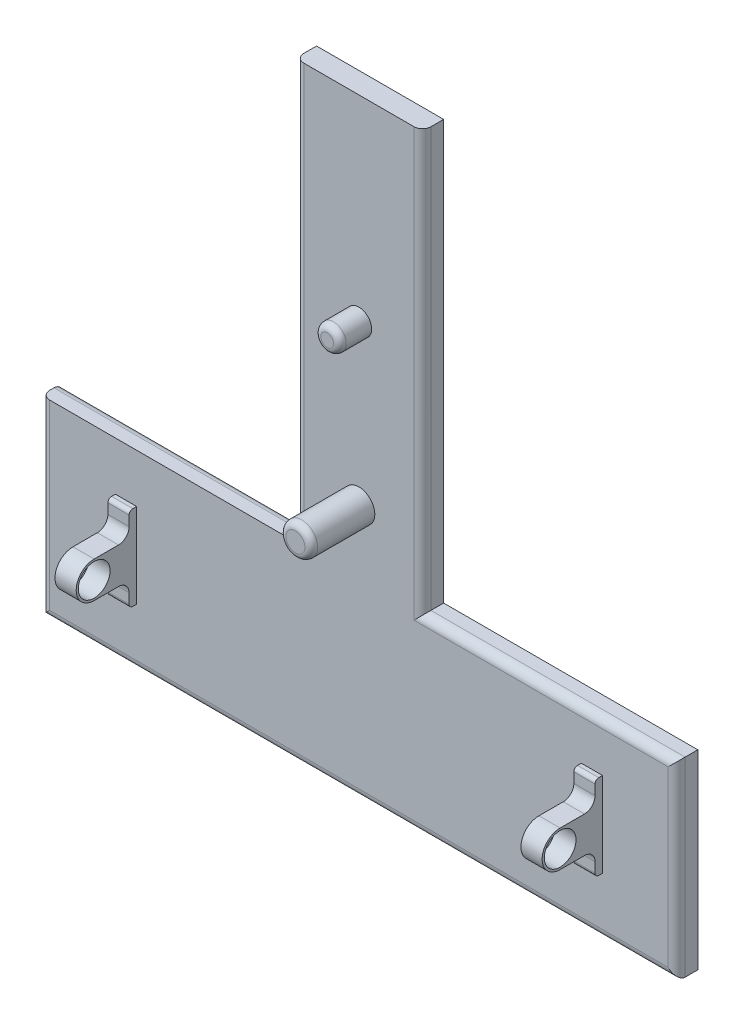
SolidWorks part; units mm, degrees
ref_plane "Front Plane" through (0, 0, 0) normal (0, 0, 1) x (1, 0, 0)
ref_plane "Top Plane" through (0, 0, 0) normal (0, 1, 0) x (1, 0, 0)
ref_plane "Right Plane" through (0, 0, 0) normal (1, 0, 0) x (0, 0, -1)
sketch "Sketch1" plane through (0, 0, 0) normal (0, 0, 1) x (1, 0, 0)
  line L0 (-150, 0) -> (150, 0)
  line L1 (150, 0) -> (150, 90)
  line L2 (150, 90) -> (30, 90)
  line L3 (30, 90) -> (30, 287.77)
  line L4 (30, 287.77) -> (-30, 287.77)
  line L5 (-30, 287.77) -> (-30, 90)
  line L6 (-30, 90) -> (-150, 90)
  line L7 (-150, 90) -> (-150, 0)
  line L8 (0, 308.6117) -> (0, -46.5858) construction
  circle A0 centre (0, 195) radius 6
  circle A1 centre (0, 120) radius 7.5
  point P3 (0, 0)
  point P12 (0, 195)
  point P13 (0, 120)
  dimension "D9" = 12
  dimension "D10" = 15
  dimension "D1" = 300
  dimension "D2" = 90
  dimension "D3" = 90
  dimension "D4" = 60
  dimension "D5" = 120
  dimension "D6" = 287.77
  dimension "D7" = 92.77
  dimension "D8" = 75
extrude "Boss-Extrude1" add sketch "Sketch1" along normal blind 10 contours L3 L4 L5 L6 L7 L0 L1 L2
extrude "Boss-Extrude2" add sketch "Sketch1<3>" along normal blind 25 contours A0
sketch "Sketch1<3>" plane through (0, 0, 0) normal (0, 0, 1) x (1, 0, 0) same geometry as "Sketch1"
extrude "Boss-Extrude3" add sketch "Sketch1<4>" along normal blind 40 contours A1
sketch "Sketch1<4>" plane through (0, 0, 0) normal (0, 0, 1) x (1, 0, 0) same geometry as "Sketch1"
fillet "Fillet1" radius 3 2 edges at (7.5, 120, 40) (6, 195, 25)
fillet "Fillet3" radius 4 7 edges at (-150, 45, 10) (0, 0, 10) (150, 45, 10) (90, 90, 10) (30, 188.885, 10) (-30, 188.885, 10) (-90, 90, 0)
sketch "Sketch2" plane through (0, 0, 0) normal (1, 0, 0) x (0, 0, -1)
  line L0 (-10, 67) -> (-10, 27)
  line L1 (-10, 4) -> (-10, 86) construction
  line L2 (-10, 27) -> (-11.76, 27)
  line L3 (-13.52, 28.76) -> (-13.52, 33.5)
  line L4 (-11.76, 67) -> (-10, 67)
  line L5 (-30, 55.5) -> (-18.52, 55.5)
  line L6 (-30, 38.5) -> (-18.52, 38.5)
  line L7 (-6, 0) -> (0, 0) construction
  line L8 (-13.52, 60.5) -> (-13.52, 65.24)
  circle A0 centre (-30, 47) radius 7.5
  arc A1 (-30, 55.5) -> (-30, 38.5) centre (-30, 47) ccw
  arc A2 (-18.52, 55.5) -> (-13.52, 60.5) centre (-18.52, 60.5) ccw
  arc A3 (-18.52, 38.5) -> (-13.52, 33.5) centre (-18.52, 33.5) cw
  arc A4 (-11.76, 27) -> (-13.52, 28.76) centre (-11.76, 28.76) cw
  arc A5 (-13.52, 65.24) -> (-11.76, 67) centre (-11.76, 65.24) cw
  point P10 (-10, 47)
  point P17 (-13.52, 55.5)
  point P22 (-13.52, 27)
  point P25 (-13.52, 67)
  dimension "D1" = 17
  dimension "D2" = 15
  dimension "D7" = 5
  dimension "D8" = 1.76
  dimension "D3" = 20
  dimension "D4" = 3.52
  dimension "D5" = 40
  dimension "D6" = 47
extrude "Boss-Extrude4" add sketch "Sketch2" along normal blind 10 from offset 105
extrude "Boss-Extrude5" add sketch "Sketch2<2>" against normal blind 10 from offset 105 offset against normal yes
sketch "Sketch2<2>" plane through (0, 0, 0) normal (1, 0, 0) x (0, 0, -1) same geometry as "Sketch2"
